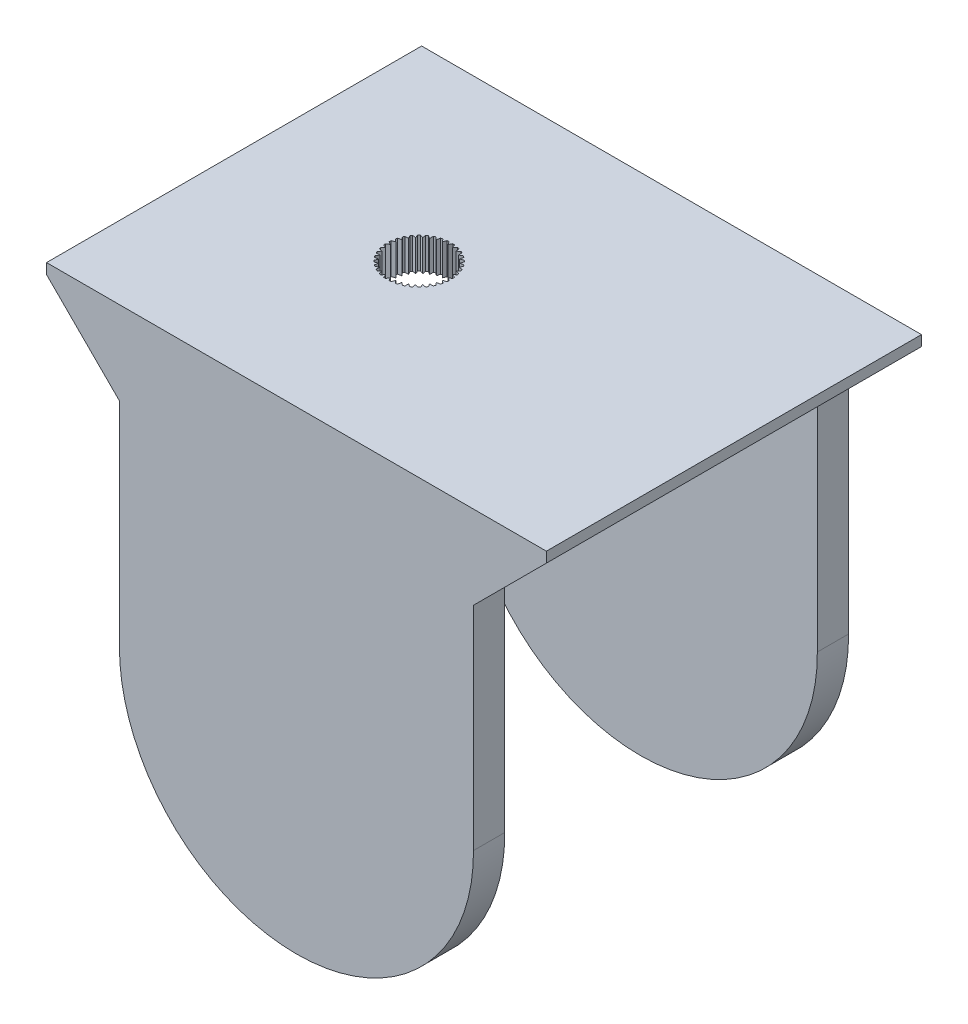
SolidWorks part; units mm, degrees
material "PLA"
ref_plane "Front Plane" through (0, 0, 0) normal (0, 0, 1) x (1, 0, 0)
ref_plane "Top Plane" through (0, 0, 0) normal (0, 1, 0) x (1, 0, 0)
ref_plane "Right Plane" through (0, 0, 0) normal (1, 0, 0) x (0, 0, -1)
sketch "Sketch1" plane through (0, 0, 0) normal (0, 1, 0) x (1, 0, 0)
  line L1 (-24, -18.01) -> (24, -18.01)
  line L2 (-24, -18.01) -> (-24, 18.01)
  line L3 (-24, 18.01) -> (24, 18.01)
  line L4 (24, -18.01) -> (24, 18.01)
  point P4 (0, 18.01)
  point P6 (-24, 0)
  dimension "D1" = 48
  dimension "D2" = 36.02
extrude "Boss-Extrude1" add sketch "Sketch1" along normal blind 3
sketch "Sketch2" plane through (0, 3, 0) normal (0, 1, 0) x (1, 0, 0)
  line L0 (2.3718, 1.5412) -> (2.4182, 1.6214) construction
  line L1 (2.3507, 1.7178) -> (2.2594, 1.7017) construction
  line L2 (2.4182, 1.6214) -> (2.4507, 1.6778) construction
  line L3 (2.4148, 1.7291) -> (2.3507, 1.7178) construction
  line L4 (2.2919, 1.4028) -> (2.3718, 1.5412) construction
  line L5 (2.2594, 1.7017) -> (2.1021, 1.6739) construction
  line L6 (2.0999, 2.0167) -> (2.1221, 2.0778) construction
  line L7 (2.0778, 2.1221) -> (2.0167, 2.0999) construction
  line L8 (2.0682, 1.9296) -> (2.0999, 2.0167) construction
  line L9 (2.0167, 2.0999) -> (1.9296, 2.0682) construction
  line L10 (2.0135, 1.7795) -> (2.0682, 1.9296) construction
  line L11 (1.9296, 2.0682) -> (1.7795, 2.0135) construction
  line L12 (1.6778, 2.4507) -> (1.6214, 2.4182) construction
  line L13 (1.7178, 2.3507) -> (1.7291, 2.4148) construction
  line L14 (1.6214, 2.4182) -> (1.5412, 2.3718) construction
  line L15 (1.7017, 2.2594) -> (1.7178, 2.3507) construction
  line L16 (1.5412, 2.3718) -> (1.4028, 2.2919) construction
  line L17 (1.6739, 2.1021) -> (1.7017, 2.2594) construction
  line L18 (2.5007, 0.9835) -> (2.6034, 1.1059) construction
  line L19 (2.5206, 1.2835) -> (2.3608, 1.2835) construction
  line L20 (2.663, 1.1768) -> (2.7048, 1.2267) construction
  line L21 (2.6783, 1.2835) -> (2.6132, 1.2835) construction
  line L22 (2.6034, 1.1059) -> (2.663, 1.1768) construction
  line L23 (2.6132, 1.2835) -> (2.5206, 1.2835) construction
  line L24 (2.8269, 0.6965) -> (2.8767, 0.7384) construction
  line L25 (2.8605, 0.7989) -> (2.7964, 0.8102) construction
  line L26 (2.7559, 0.637) -> (2.8269, 0.6965) construction
  line L27 (2.7964, 0.8102) -> (2.7052, 0.8263) construction
  line L28 (2.6335, 0.5343) -> (2.7559, 0.637) construction
  line L29 (2.7052, 0.8263) -> (2.5478, 0.854) construction
  line L30 (2.6863, 0.0689) -> (2.8247, 0.1488) construction
  line L31 (2.8076, 0.344) -> (2.6574, 0.3986) construction
  line L32 (2.8247, 0.1488) -> (2.9049, 0.1951) construction
  line L33 (2.8946, 0.3123) -> (2.8076, 0.344) construction
  line L34 (2.9049, 0.1951) -> (2.9613, 0.2276) construction
  line L35 (2.9558, 0.29) -> (2.8946, 0.3123) construction
  line L36 (2.9613, -0.2276) -> (2.9049, -0.1951) construction
  line L37 (2.8946, -0.3123) -> (2.9558, -0.29) construction
  line L38 (2.9049, -0.1951) -> (2.8247, -0.1488) construction
  line L39 (2.8076, -0.344) -> (2.8946, -0.3123) construction
  line L40 (2.8247, -0.1488) -> (2.6863, -0.0689) construction
  line L41 (2.6574, -0.3986) -> (2.8076, -0.344) construction
  line L42 (2.7964, -0.8102) -> (2.8605, -0.7989) construction
  line L43 (2.8767, -0.7384) -> (2.8269, -0.6965) construction
  line L44 (2.7052, -0.8263) -> (2.7964, -0.8102) construction
  line L45 (2.8269, -0.6965) -> (2.7559, -0.637) construction
  line L46 (2.5478, -0.854) -> (2.7052, -0.8263) construction
  line L47 (2.7559, -0.637) -> (2.6335, -0.5343) construction
  line L48 (2.5206, -1.2835) -> (2.6132, -1.2835) construction
  line L49 (2.663, -1.1768) -> (2.6034, -1.1059) construction
  line L50 (2.3608, -1.2835) -> (2.5206, -1.2835) construction
  line L51 (2.6034, -1.1059) -> (2.5007, -0.9835) construction
  line L52 (2.6863, -0.0689) -> (2.567, 0) construction
  line L53 (2.567, 0) -> (2.6863, 0.0689) construction
  line L54 (2.6574, 0.3986) -> (2.528, 0.4458) construction
  line L55 (2.528, 0.4458) -> (2.6335, 0.5343) construction
  line L56 (2.5478, 0.854) -> (2.4122, 0.878) construction
  line L57 (2.4122, 0.878) -> (2.5007, 0.9835) construction
  line L58 (2.3608, 1.2835) -> (2.2231, 1.2835) construction
  line L59 (2.2231, 1.2835) -> (2.2919, 1.4028) construction
  line L60 (2.1021, 1.6739) -> (1.9664, 1.65) construction
  line L61 (1.9664, 1.65) -> (2.0135, 1.7795) construction
  line L62 (1.7795, 2.0135) -> (1.65, 1.9664) construction
  line L63 (1.65, 1.9664) -> (1.6739, 2.1021) construction
  line L64 (1.4028, 2.2919) -> (1.2835, 2.2231) construction
  line L65 (1.2835, 2.2231) -> (1.2835, 2.3608) construction
  line L66 (0.9835, 2.5007) -> (0.878, 2.4122) construction
  line L67 (0.878, 2.4122) -> (0.854, 2.5478) construction
  line L68 (0.5343, 2.6335) -> (0.4458, 2.528) construction
  line L69 (0.4458, 2.528) -> (0.3986, 2.6574) construction
  line L70 (0.0689, 2.6863) -> (0, 2.567) construction
  line L71 (0, 2.567) -> (-0.0689, 2.6863) construction
  line L72 (-0.3986, 2.6574) -> (-0.4458, 2.528) construction
  line L73 (-0.4458, 2.528) -> (-0.5343, 2.6335) construction
  line L74 (-0.854, 2.5478) -> (-0.878, 2.4122) construction
  line L75 (-0.878, 2.4122) -> (-0.9835, 2.5007) construction
  line L76 (-1.2835, 2.3608) -> (-1.2835, 2.2231) construction
  line L77 (-1.2835, 2.2231) -> (-1.4028, 2.2919) construction
  line L78 (-1.6739, 2.1021) -> (-1.65, 1.9664) construction
  line L79 (-1.65, 1.9664) -> (-1.7795, 2.0135) construction
  line L80 (-2.0135, 1.7795) -> (-1.9664, 1.65) construction
  line L81 (-1.9664, 1.65) -> (-2.1021, 1.6739) construction
  line L82 (-2.2919, 1.4028) -> (-2.2231, 1.2835) construction
  line L83 (-2.2231, 1.2835) -> (-2.3608, 1.2835) construction
  line L84 (-2.5007, 0.9835) -> (-2.4122, 0.878) construction
  line L85 (-2.4122, 0.878) -> (-2.5478, 0.854) construction
  line L86 (-2.6335, 0.5343) -> (-2.528, 0.4458) construction
  line L87 (-2.528, 0.4458) -> (-2.6574, 0.3986) construction
  line L88 (-2.6863, 0.0689) -> (-2.567, 0) construction
  line L89 (-2.567, 0) -> (-2.6863, -0.0689) construction
  line L90 (-2.6574, -0.3986) -> (-2.528, -0.4458) construction
  line L91 (-2.528, -0.4458) -> (-2.6335, -0.5343) construction
  line L92 (-2.5478, -0.854) -> (-2.4122, -0.878) construction
  line L93 (-2.4122, -0.878) -> (-2.5007, -0.9835) construction
  line L94 (-2.3608, -1.2835) -> (-2.2231, -1.2835) construction
  line L95 (-2.2231, -1.2835) -> (-2.2919, -1.4028) construction
  line L96 (-2.1021, -1.6739) -> (-1.9664, -1.65) construction
  line L97 (-1.9664, -1.65) -> (-2.0135, -1.7795) construction
  line L98 (-1.7795, -2.0135) -> (-1.65, -1.9664) construction
  line L99 (-1.65, -1.9664) -> (-1.6739, -2.1021) construction
  line L100 (-1.4028, -2.2919) -> (-1.2835, -2.2231) construction
  line L101 (-1.2835, -2.2231) -> (-1.2835, -2.3608) construction
  line L102 (-0.9835, -2.5007) -> (-0.878, -2.4122) construction
  line L103 (-0.878, -2.4122) -> (-0.854, -2.5478) construction
  line L104 (-0.5343, -2.6335) -> (-0.4458, -2.528) construction
  line L105 (-0.4458, -2.528) -> (-0.3986, -2.6574) construction
  line L106 (-0.0689, -2.6863) -> (0, -2.567) construction
  line L107 (0, -2.567) -> (0.0689, -2.6863) construction
  line L108 (0.3986, -2.6574) -> (0.4458, -2.528) construction
  line L109 (0.4458, -2.528) -> (0.5343, -2.6335) construction
  line L110 (0.854, -2.5478) -> (0.878, -2.4122) construction
  line L111 (0.878, -2.4122) -> (0.9835, -2.5007) construction
  line L112 (1.2835, -2.3608) -> (1.2835, -2.2231) construction
  line L113 (1.2835, -2.2231) -> (1.4028, -2.2919) construction
  line L114 (1.6739, -2.1021) -> (1.65, -1.9664) construction
  line L115 (1.65, -1.9664) -> (1.7795, -2.0135) construction
  line L116 (2.0135, -1.7795) -> (1.9664, -1.65) construction
  line L117 (1.9664, -1.65) -> (2.1021, -1.6739) construction
  line L118 (2.2919, -1.4028) -> (2.2231, -1.2835) construction
  line L119 (2.2231, -1.2835) -> (2.3608, -1.2835) construction
  line L120 (2.5007, -0.9835) -> (2.4122, -0.878) construction
  line L121 (2.4122, -0.878) -> (2.5478, -0.854) construction
  line L122 (2.6335, -0.5343) -> (2.528, -0.4458) construction
  line L123 (2.528, -0.4458) -> (2.6574, -0.3986) construction
  line L124 (2.6132, -1.2835) -> (2.6783, -1.2835) construction
  line L125 (2.7048, -1.2267) -> (2.663, -1.1768) construction
  line L126 (2.4507, -1.6778) -> (2.4182, -1.6214) construction
  line L127 (2.3507, -1.7178) -> (2.4148, -1.7291) construction
  line L128 (2.4182, -1.6214) -> (2.3718, -1.5412) construction
  line L129 (2.2594, -1.7017) -> (2.3507, -1.7178) construction
  line L130 (1.7795, -2.0135) -> (1.9296, -2.0682) construction
  line L131 (2.0682, -1.9296) -> (2.0135, -1.7795) construction
  line L132 (1.9296, -2.0682) -> (2.0167, -2.0999) construction
  line L133 (2.0999, -2.0167) -> (2.0682, -1.9296) construction
  line L134 (2.0167, -2.0999) -> (2.0778, -2.1221) construction
  line L135 (2.1221, -2.0778) -> (2.0999, -2.0167) construction
  line L136 (2.3718, -1.5412) -> (2.2919, -1.4028) construction
  line L137 (2.1021, -1.6739) -> (2.2594, -1.7017) construction
  line L138 (1.7291, -2.4148) -> (1.7178, -2.3507) construction
  line L139 (1.6214, -2.4182) -> (1.6778, -2.4507) construction
  line L140 (1.7178, -2.3507) -> (1.7017, -2.2594) construction
  line L141 (1.5412, -2.3718) -> (1.6214, -2.4182) construction
  line L142 (1.7017, -2.2594) -> (1.6739, -2.1021) construction
  line L143 (1.4028, -2.2919) -> (1.5412, -2.3718) construction
  line L144 (-0.3123, -2.8946) -> (-0.29, -2.9558) construction
  line L145 (-0.2276, -2.9613) -> (-0.1951, -2.9049) construction
  line L146 (-0.344, -2.8076) -> (-0.3123, -2.8946) construction
  line L147 (-0.1951, -2.9049) -> (-0.1488, -2.8247) construction
  line L148 (0.344, -2.8076) -> (0.3986, -2.6574) construction
  line L149 (0.0689, -2.6863) -> (0.1488, -2.8247) construction
  line L150 (0.3123, -2.8946) -> (0.344, -2.8076) construction
  line L151 (0.1488, -2.8247) -> (0.1951, -2.9049) construction
  line L152 (0.29, -2.9558) -> (0.3123, -2.8946) construction
  line L153 (0.1951, -2.9049) -> (0.2276, -2.9613) construction
  line L154 (0.6965, -2.8269) -> (0.7384, -2.8767) construction
  line L155 (0.7989, -2.8605) -> (0.8102, -2.7964) construction
  line L156 (1.1768, -2.663) -> (1.2267, -2.7048) construction
  line L157 (1.2835, -2.6783) -> (1.2835, -2.6132) construction
  line L158 (1.1059, -2.6034) -> (1.1768, -2.663) construction
  line L159 (1.2835, -2.6132) -> (1.2835, -2.5206) construction
  line L160 (0.9835, -2.5007) -> (1.1059, -2.6034) construction
  line L161 (1.2835, -2.5206) -> (1.2835, -2.3608) construction
  line L162 (0.637, -2.7559) -> (0.6965, -2.8269) construction
  line L163 (0.8102, -2.7964) -> (0.8263, -2.7052) construction
  line L164 (0.5343, -2.6335) -> (0.637, -2.7559) construction
  line L165 (0.8263, -2.7052) -> (0.854, -2.5478) construction
  line L166 (-0.3986, -2.6574) -> (-0.344, -2.8076) construction
  line L167 (-0.1488, -2.8247) -> (-0.0689, -2.6863) construction
  line L168 (-0.8102, -2.7964) -> (-0.7989, -2.8605) construction
  line L169 (-0.7384, -2.8767) -> (-0.6965, -2.8269) construction
  line L170 (-0.8263, -2.7052) -> (-0.8102, -2.7964) construction
  line L171 (-0.6965, -2.8269) -> (-0.637, -2.7559) construction
  line L172 (-0.854, -2.5478) -> (-0.8263, -2.7052) construction
  line L173 (-0.637, -2.7559) -> (-0.5343, -2.6335) construction
  line L174 (-1.2835, -2.6132) -> (-1.2835, -2.6783) construction
  line L175 (-1.2267, -2.7048) -> (-1.1768, -2.663) construction
  line L176 (-1.2835, -2.5206) -> (-1.2835, -2.6132) construction
  line L177 (-1.1768, -2.663) -> (-1.1059, -2.6034) construction
  line L178 (-1.2835, -2.3608) -> (-1.2835, -2.5206) construction
  line L179 (-1.1059, -2.6034) -> (-0.9835, -2.5007) construction
  line L180 (-1.7178, -2.3507) -> (-1.7291, -2.4148) construction
  line L181 (-1.6778, -2.4507) -> (-1.6214, -2.4182) construction
  line L182 (-1.7017, -2.2594) -> (-1.7178, -2.3507) construction
  line L183 (-1.6214, -2.4182) -> (-1.5412, -2.3718) construction
  line L184 (-1.6739, -2.1021) -> (-1.7017, -2.2594) construction
  line L185 (-1.5412, -2.3718) -> (-1.4028, -2.2919) construction
  line L186 (-2.0999, -2.0167) -> (-2.1221, -2.0778) construction
  line L187 (-2.0778, -2.1221) -> (-2.0167, -2.0999) construction
  line L188 (-2.0682, -1.9296) -> (-2.0999, -2.0167) construction
  line L189 (-2.0167, -2.0999) -> (-1.9296, -2.0682) construction
  line L190 (-2.0135, -1.7795) -> (-2.0682, -1.9296) construction
  line L191 (-1.9296, -2.0682) -> (-1.7795, -2.0135) construction
  line L192 (-2.4148, -1.7291) -> (-2.3507, -1.7178) construction
  line L193 (-2.4182, -1.6214) -> (-2.4507, -1.6778) construction
  line L194 (-2.3507, -1.7178) -> (-2.2594, -1.7017) construction
  line L195 (-2.3718, -1.5412) -> (-2.4182, -1.6214) construction
  line L196 (-2.2594, -1.7017) -> (-2.1021, -1.6739) construction
  line L197 (-2.2919, -1.4028) -> (-2.3718, -1.5412) construction
  line L198 (-2.6783, -1.2835) -> (-2.6132, -1.2835) construction
  line L199 (-2.663, -1.1768) -> (-2.7048, -1.2267) construction
  line L200 (-2.6132, -1.2835) -> (-2.5206, -1.2835) construction
  line L201 (-2.6034, -1.1059) -> (-2.663, -1.1768) construction
  line L202 (-2.5206, -1.2835) -> (-2.3608, -1.2835) construction
  line L203 (-2.5007, -0.9835) -> (-2.6034, -1.1059) construction
  line L204 (-2.8605, -0.7989) -> (-2.7964, -0.8102) construction
  line L205 (-2.8269, -0.6965) -> (-2.8767, -0.7384) construction
  line L206 (-2.7964, -0.8102) -> (-2.7052, -0.8263) construction
  line L207 (-2.7559, -0.637) -> (-2.8269, -0.6965) construction
  line L208 (-2.7052, -0.8263) -> (-2.5478, -0.854) construction
  line L209 (-2.6335, -0.5343) -> (-2.7559, -0.637) construction
  line L210 (-2.9558, -0.29) -> (-2.8946, -0.3123) construction
  line L211 (-2.9049, -0.1951) -> (-2.9613, -0.2276) construction
  line L212 (-2.8076, -0.344) -> (-2.6574, -0.3986) construction
  line L213 (-2.6863, -0.0689) -> (-2.8247, -0.1488) construction
  line L214 (-2.8946, -0.3123) -> (-2.8076, -0.344) construction
  line L215 (-2.8247, -0.1488) -> (-2.9049, -0.1951) construction
  line L216 (-2.9613, 0.2276) -> (-2.9049, 0.1951) construction
  line L217 (-2.8946, 0.3123) -> (-2.9558, 0.29) construction
  line L218 (-2.9049, 0.1951) -> (-2.8247, 0.1488) construction
  line L219 (-2.8076, 0.344) -> (-2.8946, 0.3123) construction
  line L220 (-2.8247, 0.1488) -> (-2.6863, 0.0689) construction
  line L221 (-2.6574, 0.3986) -> (-2.8076, 0.344) construction
  line L222 (-2.8269, 0.6965) -> (-2.7559, 0.637) construction
  line L223 (-2.7052, 0.8263) -> (-2.7964, 0.8102) construction
  line L224 (-2.8767, 0.7384) -> (-2.8269, 0.6965) construction
  line L225 (-2.7964, 0.8102) -> (-2.8605, 0.7989) construction
  line L226 (-2.7559, 0.637) -> (-2.6335, 0.5343) construction
  line L227 (-2.5478, 0.854) -> (-2.7052, 0.8263) construction
  line L228 (-2.663, 1.1768) -> (-2.6034, 1.1059) construction
  line L229 (-2.5206, 1.2835) -> (-2.6132, 1.2835) construction
  line L230 (-2.7048, 1.2267) -> (-2.663, 1.1768) construction
  line L231 (-2.6132, 1.2835) -> (-2.6783, 1.2835) construction
  line L232 (-2.6034, 1.1059) -> (-2.5007, 0.9835) construction
  line L233 (-2.3608, 1.2835) -> (-2.5206, 1.2835) construction
  line L234 (-2.4507, 1.6778) -> (-2.4182, 1.6214) construction
  line L235 (-2.3507, 1.7178) -> (-2.4148, 1.7291) construction
  line L236 (-2.4182, 1.6214) -> (-2.3718, 1.5412) construction
  line L237 (-2.2594, 1.7017) -> (-2.3507, 1.7178) construction
  line L238 (-2.3718, 1.5412) -> (-2.2919, 1.4028) construction
  line L239 (-2.1021, 1.6739) -> (-2.2594, 1.7017) construction
  line L240 (-2.0167, 2.0999) -> (-2.0778, 2.1221) construction
  line L241 (-2.1221, 2.0778) -> (-2.0999, 2.0167) construction
  line L242 (-1.9296, 2.0682) -> (-2.0167, 2.0999) construction
  line L243 (-2.0999, 2.0167) -> (-2.0682, 1.9296) construction
  line L244 (-1.7795, 2.0135) -> (-1.9296, 2.0682) construction
  line L245 (-2.0682, 1.9296) -> (-2.0135, 1.7795) construction
  line L246 (-1.7291, 2.4148) -> (-1.7178, 2.3507) construction
  line L247 (-1.6214, 2.4182) -> (-1.6778, 2.4507) construction
  line L248 (-1.7178, 2.3507) -> (-1.7017, 2.2594) construction
  line L249 (-1.5412, 2.3718) -> (-1.6214, 2.4182) construction
  line L250 (-1.7017, 2.2594) -> (-1.6739, 2.1021) construction
  line L251 (-1.4028, 2.2919) -> (-1.5412, 2.3718) construction
  line L252 (-1.2835, 2.6783) -> (-1.2835, 2.6132) construction
  line L253 (-1.1768, 2.663) -> (-1.2267, 2.7048) construction
  line L254 (-1.2835, 2.6132) -> (-1.2835, 2.5206) construction
  line L255 (-1.1059, 2.6034) -> (-1.1768, 2.663) construction
  line L256 (-1.2835, 2.5206) -> (-1.2835, 2.3608) construction
  line L257 (-0.9835, 2.5007) -> (-1.1059, 2.6034) construction
  line L258 (-0.7989, 2.8605) -> (-0.8102, 2.7964) construction
  line L259 (-0.6965, 2.8269) -> (-0.7384, 2.8767) construction
  line L260 (-0.8102, 2.7964) -> (-0.8263, 2.7052) construction
  line L261 (-0.637, 2.7559) -> (-0.6965, 2.8269) construction
  line L262 (-0.8263, 2.7052) -> (-0.854, 2.5478) construction
  line L263 (-0.5343, 2.6335) -> (-0.637, 2.7559) construction
  line L264 (1.1768, 2.663) -> (1.1059, 2.6034) construction
  line L265 (1.2835, 2.5206) -> (1.2835, 2.6132) construction
  line L266 (1.2267, 2.7048) -> (1.1768, 2.663) construction
  line L267 (1.2835, 2.6132) -> (1.2835, 2.6783) construction
  line L268 (1.1059, 2.6034) -> (0.9835, 2.5007) construction
  line L269 (1.2835, 2.3608) -> (1.2835, 2.5206) construction
  line L270 (0.8102, 2.7964) -> (0.7989, 2.8605) construction
  line L271 (0.7384, 2.8767) -> (0.6965, 2.8269) construction
  line L272 (0.8263, 2.7052) -> (0.8102, 2.7964) construction
  line L273 (0.6965, 2.8269) -> (0.637, 2.7559) construction
  line L274 (0.854, 2.5478) -> (0.8263, 2.7052) construction
  line L275 (0.637, 2.7559) -> (0.5343, 2.6335) construction
  line L276 (0.3123, 2.8946) -> (0.29, 2.9558) construction
  line L277 (0.2276, 2.9613) -> (0.1951, 2.9049) construction
  line L278 (0.344, 2.8076) -> (0.3123, 2.8946) construction
  line L279 (0.1951, 2.9049) -> (0.1488, 2.8247) construction
  line L280 (0.3986, 2.6574) -> (0.344, 2.8076) construction
  line L281 (0.1488, 2.8247) -> (0.0689, 2.6863) construction
  line L282 (-0.29, 2.9558) -> (-0.3123, 2.8946) construction
  line L283 (-0.1951, 2.9049) -> (-0.2276, 2.9613) construction
  line L284 (-0.3123, 2.8946) -> (-0.344, 2.8076) construction
  line L285 (-0.1488, 2.8247) -> (-0.1951, 2.9049) construction
  line L286 (-0.344, 2.8076) -> (-0.3986, 2.6574) construction
  line L287 (-0.0689, 2.6863) -> (-0.1488, 2.8247) construction
  line L288 (2.4584, 1.4912) -> (2.5048, 1.5714)
  line L289 (2.5048, 1.5714) -> (2.5684, 1.6817)
  line L290 (2.4587, 1.8384) -> (2.3333, 1.8163)
  line L291 (2.3333, 1.8163) -> (2.2421, 1.8002)
  line L292 (2.2421, 1.8002) -> (2.1196, 1.7786)
  line L293 (2.1196, 1.7786) -> (2.1196, 1.7786)
  line L294 (2.1196, 1.7786) -> (2.1196, 1.7786)
  line L295 (2.1196, 1.7786) -> (2.1622, 1.8954)
  line L296 (2.1622, 1.8954) -> (2.1938, 1.9825)
  line L297 (2.1938, 1.9825) -> (2.2374, 2.1021)
  line L298 (2.1021, 2.2374) -> (1.9825, 2.1938)
  line L299 (1.9825, 2.1938) -> (1.8954, 2.1622)
  line L300 (1.8954, 2.1622) -> (1.7786, 2.1196)
  line L301 (1.7786, 2.1196) -> (1.7786, 2.1196)
  line L302 (1.7786, 2.1196) -> (1.7786, 2.1196)
  line L303 (1.7786, 2.1196) -> (1.8002, 2.2421)
  line L304 (1.8002, 2.2421) -> (1.8163, 2.3333)
  line L305 (1.8163, 2.3333) -> (1.8384, 2.4587)
  line L306 (1.6817, 2.5684) -> (1.5714, 2.5048)
  line L307 (1.5714, 2.5048) -> (1.4912, 2.4584)
  line L308 (1.4912, 2.4584) -> (1.3835, 2.3963)
  line L309 (1.3835, 2.3963) -> (1.3835, 2.3963)
  line L310 (1.3835, 2.3963) -> (1.3835, 2.3963)
  line L311 (1.3835, 2.3963) -> (1.3835, 2.5206)
  line L312 (1.3835, 2.5206) -> (1.3835, 2.6132)
  line L313 (1.3835, 2.6132) -> (1.3835, 2.7406)
  line L314 (1.2101, 2.8214) -> (1.1126, 2.7396)
  line L315 (1.1126, 2.7396) -> (1.0416, 2.68)
  line L316 (1.0416, 2.68) -> (0.9464, 2.6001)
  line L317 (0.9464, 2.6001) -> (0.9464, 2.6001)
  line L318 (0.9464, 2.6001) -> (0.9464, 2.6001)
  line L319 (0.9464, 2.6001) -> (0.9248, 2.7226)
  line L320 (0.9248, 2.7226) -> (0.9087, 2.8138)
  line L321 (0.9087, 2.8138) -> (0.8866, 2.9392)
  line L322 (0.7018, 2.9887) -> (0.6199, 2.8911)
  line L323 (0.6199, 2.8911) -> (0.5604, 2.8202)
  line L324 (0.5604, 2.8202) -> (0.4805, 2.725)
  line L325 (0.4805, 2.725) -> (0.4805, 2.725)
  line L326 (0.4805, 2.725) -> (0.4805, 2.725)
  line L327 (0.4805, 2.725) -> (0.438, 2.8418)
  line L328 (0.438, 2.8418) -> (0.4063, 2.9288)
  line L329 (0.4063, 2.9288) -> (0.3627, 3.0485)
  line L330 (0.1722, 3.0652) -> (0.1085, 2.9549)
  line L331 (0.1085, 2.9549) -> (0.0622, 2.8747)
  line L332 (0.0622, 2.8747) -> (0, 2.767)
  line L333 (0, 2.767) -> (0, 2.767)
  line L334 (0, 2.767) -> (0, 2.767)
  line L335 (0, 2.767) -> (-0.0622, 2.8747)
  line L336 (-0.0622, 2.8747) -> (-0.1085, 2.9549)
  line L337 (-0.1085, 2.9549) -> (-0.1722, 3.0652)
  line L338 (-0.3627, 3.0485) -> (-0.4063, 2.9288)
  line L339 (-0.4063, 2.9288) -> (-0.438, 2.8418)
  line L340 (-0.438, 2.8418) -> (-0.4805, 2.725)
  line L341 (-0.4805, 2.725) -> (-0.4805, 2.725)
  line L342 (-0.4805, 2.725) -> (-0.4805, 2.725)
  line L343 (-0.4805, 2.725) -> (-0.5604, 2.8202)
  line L344 (-0.5604, 2.8202) -> (-0.6199, 2.8911)
  line L345 (-0.6199, 2.8911) -> (-0.7018, 2.9887)
  line L346 (-0.8866, 2.9392) -> (-0.9087, 2.8138)
  line L347 (-0.9087, 2.8138) -> (-0.9248, 2.7226)
  line L348 (-0.9248, 2.7226) -> (-0.9464, 2.6001)
  line L349 (-0.9464, 2.6001) -> (-0.9464, 2.6001)
  line L350 (-0.9464, 2.6001) -> (-0.9464, 2.6001)
  line L351 (-0.9464, 2.6001) -> (-1.0416, 2.68)
  line L352 (-1.0416, 2.68) -> (-1.1126, 2.7396)
  line L353 (-1.1126, 2.7396) -> (-1.2101, 2.8214)
  line L354 (-1.3835, 2.7406) -> (-1.3835, 2.6132)
  line L355 (-1.3835, 2.6132) -> (-1.3835, 2.5206)
  line L356 (-1.3835, 2.5206) -> (-1.3835, 2.3963)
  line L357 (-1.3835, 2.3963) -> (-1.3835, 2.3963)
  line L358 (-1.3835, 2.3963) -> (-1.3835, 2.3963)
  line L359 (-1.3835, 2.3963) -> (-1.4912, 2.4584)
  line L360 (-1.4912, 2.4584) -> (-1.5714, 2.5048)
  line L361 (-1.5714, 2.5048) -> (-1.6817, 2.5684)
  line L362 (-1.8384, 2.4587) -> (-1.8163, 2.3333)
  line L363 (-1.8163, 2.3333) -> (-1.8002, 2.2421)
  line L364 (-1.8002, 2.2421) -> (-1.7786, 2.1196)
  line L365 (-1.7786, 2.1196) -> (-1.7786, 2.1196)
  line L366 (-1.7786, 2.1196) -> (-1.7786, 2.1196)
  line L367 (-1.7786, 2.1196) -> (-1.8954, 2.1622)
  line L368 (-1.8954, 2.1622) -> (-1.9825, 2.1938)
  line L369 (-1.9825, 2.1938) -> (-2.1021, 2.2374)
  line L370 (-2.2374, 2.1021) -> (-2.1938, 1.9825)
  line L371 (-2.1938, 1.9825) -> (-2.1622, 1.8954)
  line L372 (-2.1622, 1.8954) -> (-2.1196, 1.7786)
  line L373 (-2.1196, 1.7786) -> (-2.1196, 1.7786)
  line L374 (-2.1196, 1.7786) -> (-2.1196, 1.7786)
  line L375 (-2.1196, 1.7786) -> (-2.2421, 1.8002)
  line L376 (-2.2421, 1.8002) -> (-2.3333, 1.8163)
  line L377 (-2.3333, 1.8163) -> (-2.4587, 1.8384)
  line L378 (-2.5684, 1.6817) -> (-2.5048, 1.5714)
  line L379 (-2.5048, 1.5714) -> (-2.4584, 1.4912)
  line L380 (-2.4584, 1.4912) -> (-2.3963, 1.3835)
  line L381 (-2.3963, 1.3835) -> (-2.3963, 1.3835)
  line L382 (-2.3963, 1.3835) -> (-2.3963, 1.3835)
  line L383 (-2.3963, 1.3835) -> (-2.5206, 1.3835)
  line L384 (-2.5206, 1.3835) -> (-2.6132, 1.3835)
  line L385 (-2.6132, 1.3835) -> (-2.7406, 1.3835)
  line L386 (-2.8214, 1.2101) -> (-2.7396, 1.1126)
  line L387 (-2.7396, 1.1126) -> (-2.68, 1.0416)
  line L388 (-2.68, 1.0416) -> (-2.6001, 0.9464)
  line L389 (-2.6001, 0.9464) -> (-2.6001, 0.9464)
  line L390 (-2.6001, 0.9464) -> (-2.6001, 0.9464)
  line L391 (-2.6001, 0.9464) -> (-2.7226, 0.9248)
  line L392 (-2.7226, 0.9248) -> (-2.8138, 0.9087)
  line L393 (-2.8138, 0.9087) -> (-2.9392, 0.8866)
  line L394 (-2.9887, 0.7018) -> (-2.8911, 0.6199)
  line L395 (-2.8911, 0.6199) -> (-2.8202, 0.5604)
  line L396 (-2.8202, 0.5604) -> (-2.725, 0.4805)
  line L397 (-2.725, 0.4805) -> (-2.725, 0.4805)
  line L398 (-2.725, 0.4805) -> (-2.725, 0.4805)
  line L399 (-2.725, 0.4805) -> (-2.8418, 0.438)
  line L400 (-2.8418, 0.438) -> (-2.9288, 0.4063)
  line L401 (-2.9288, 0.4063) -> (-3.0485, 0.3627)
  line L402 (-3.0652, 0.1722) -> (-2.9549, 0.1085)
  line L403 (-2.9549, 0.1085) -> (-2.8747, 0.0622)
  line L404 (-2.8747, 0.0622) -> (-2.767, 0)
  line L405 (-2.767, 0) -> (-2.767, 0)
  line L406 (-2.767, 0) -> (-2.767, 0)
  line L407 (-2.767, 0) -> (-2.8747, -0.0622)
  line L408 (-2.8747, -0.0622) -> (-2.9549, -0.1085)
  line L409 (-2.9549, -0.1085) -> (-3.0652, -0.1722)
  line L410 (-3.0485, -0.3627) -> (-2.9288, -0.4063)
  line L411 (-2.9288, -0.4063) -> (-2.8418, -0.438)
  line L412 (-2.8418, -0.438) -> (-2.725, -0.4805)
  line L413 (-2.725, -0.4805) -> (-2.725, -0.4805)
  line L414 (-2.725, -0.4805) -> (-2.725, -0.4805)
  line L415 (-2.725, -0.4805) -> (-2.8202, -0.5604)
  line L416 (-2.8202, -0.5604) -> (-2.8911, -0.6199)
  line L417 (-2.8911, -0.6199) -> (-2.9887, -0.7018)
  line L418 (-2.9392, -0.8866) -> (-2.8138, -0.9087)
  line L419 (-2.8138, -0.9087) -> (-2.7226, -0.9248)
  line L420 (-2.7226, -0.9248) -> (-2.6001, -0.9464)
  line L421 (-2.6001, -0.9464) -> (-2.6001, -0.9464)
  line L422 (-2.6001, -0.9464) -> (-2.6001, -0.9464)
  line L423 (-2.6001, -0.9464) -> (-2.68, -1.0416)
  line L424 (-2.68, -1.0416) -> (-2.7396, -1.1126)
  line L425 (-2.7396, -1.1126) -> (-2.8214, -1.2101)
  line L426 (-2.7406, -1.3835) -> (-2.6132, -1.3835)
  line L427 (-2.6132, -1.3835) -> (-2.5206, -1.3835)
  line L428 (-2.5206, -1.3835) -> (-2.3963, -1.3835)
  line L429 (-2.3963, -1.3835) -> (-2.3963, -1.3835)
  line L430 (-2.3963, -1.3835) -> (-2.3963, -1.3835)
  line L431 (-2.3963, -1.3835) -> (-2.4584, -1.4912)
  line L432 (-2.4584, -1.4912) -> (-2.5048, -1.5714)
  line L433 (-2.5048, -1.5714) -> (-2.5684, -1.6817)
  line L434 (-2.4587, -1.8384) -> (-2.3333, -1.8163)
  line L435 (-2.3333, -1.8163) -> (-2.2421, -1.8002)
  line L436 (-2.2421, -1.8002) -> (-2.1196, -1.7786)
  line L437 (-2.1196, -1.7786) -> (-2.1196, -1.7786)
  line L438 (-2.1196, -1.7786) -> (-2.1196, -1.7786)
  line L439 (-2.1196, -1.7786) -> (-2.1622, -1.8954)
  line L440 (-2.1622, -1.8954) -> (-2.1938, -1.9825)
  line L441 (-2.1938, -1.9825) -> (-2.2374, -2.1021)
  line L442 (-2.1021, -2.2374) -> (-1.9825, -2.1938)
  line L443 (-1.9825, -2.1938) -> (-1.8954, -2.1622)
  line L444 (-1.8954, -2.1622) -> (-1.7786, -2.1196)
  line L445 (-1.7786, -2.1196) -> (-1.7786, -2.1196)
  line L446 (-1.7786, -2.1196) -> (-1.7786, -2.1196)
  line L447 (-1.7786, -2.1196) -> (-1.8002, -2.2421)
  line L448 (-1.8002, -2.2421) -> (-1.8163, -2.3333)
  line L449 (-1.8163, -2.3333) -> (-1.8384, -2.4587)
  line L450 (-1.6817, -2.5684) -> (-1.5714, -2.5048)
  line L451 (-1.5714, -2.5048) -> (-1.4912, -2.4584)
  line L452 (-1.4912, -2.4584) -> (-1.3835, -2.3963)
  line L453 (-1.3835, -2.3963) -> (-1.3835, -2.3963)
  line L454 (-1.3835, -2.3963) -> (-1.3835, -2.3963)
  line L455 (-1.3835, -2.3963) -> (-1.3835, -2.5206)
  line L456 (-1.3835, -2.5206) -> (-1.3835, -2.6132)
  line L457 (-1.3835, -2.6132) -> (-1.3835, -2.7406)
  line L458 (-1.2101, -2.8214) -> (-1.1126, -2.7396)
  line L459 (-1.1126, -2.7396) -> (-1.0416, -2.68)
  line L460 (-1.0416, -2.68) -> (-0.9464, -2.6001)
  line L461 (-0.9464, -2.6001) -> (-0.9464, -2.6001)
  line L462 (-0.9464, -2.6001) -> (-0.9464, -2.6001)
  line L463 (-0.9464, -2.6001) -> (-0.9248, -2.7226)
  line L464 (-0.9248, -2.7226) -> (-0.9087, -2.8138)
  line L465 (-0.9087, -2.8138) -> (-0.8866, -2.9392)
  line L466 (-0.7018, -2.9887) -> (-0.6199, -2.8911)
  line L467 (-0.6199, -2.8911) -> (-0.5604, -2.8202)
  line L468 (-0.5604, -2.8202) -> (-0.4805, -2.725)
  line L469 (-0.4805, -2.725) -> (-0.4805, -2.725)
  line L470 (-0.4805, -2.725) -> (-0.4805, -2.725)
  line L471 (-0.4805, -2.725) -> (-0.438, -2.8418)
  line L472 (-0.438, -2.8418) -> (-0.4063, -2.9288)
  line L473 (-0.4063, -2.9288) -> (-0.3627, -3.0485)
  line L474 (-0.1722, -3.0652) -> (-0.1085, -2.9549)
  line L475 (-0.1085, -2.9549) -> (-0.0622, -2.8747)
  line L476 (-0.0622, -2.8747) -> (0, -2.767)
  line L477 (0, -2.767) -> (0, -2.767)
  line L478 (0, -2.767) -> (0, -2.767)
  line L479 (0, -2.767) -> (0.0622, -2.8747)
  line L480 (0.0622, -2.8747) -> (0.1085, -2.9549)
  line L481 (0.1085, -2.9549) -> (0.1722, -3.0652)
  line L482 (0.3627, -3.0485) -> (0.4063, -2.9288)
  line L483 (0.4063, -2.9288) -> (0.438, -2.8418)
  line L484 (0.438, -2.8418) -> (0.4805, -2.725)
  line L485 (0.4805, -2.725) -> (0.4805, -2.725)
  line L486 (0.4805, -2.725) -> (0.4805, -2.725)
  line L487 (0.4805, -2.725) -> (0.5604, -2.8202)
  line L488 (0.5604, -2.8202) -> (0.6199, -2.8911)
  line L489 (0.6199, -2.8911) -> (0.7018, -2.9887)
  line L490 (0.8866, -2.9392) -> (0.9087, -2.8138)
  line L491 (0.9087, -2.8138) -> (0.9248, -2.7226)
  line L492 (0.9248, -2.7226) -> (0.9464, -2.6001)
  line L493 (0.9464, -2.6001) -> (0.9464, -2.6001)
  line L494 (0.9464, -2.6001) -> (0.9464, -2.6001)
  line L495 (0.9464, -2.6001) -> (1.0416, -2.68)
  line L496 (1.0416, -2.68) -> (1.1126, -2.7396)
  line L497 (1.1126, -2.7396) -> (1.2101, -2.8214)
  line L498 (1.3835, -2.7406) -> (1.3835, -2.6132)
  line L499 (1.3835, -2.6132) -> (1.3835, -2.5206)
  line L500 (1.3835, -2.5206) -> (1.3835, -2.3963)
  line L501 (1.3835, -2.3963) -> (1.3835, -2.3963)
  line L502 (1.3835, -2.3963) -> (1.3835, -2.3963)
  line L503 (1.3835, -2.3963) -> (1.4912, -2.4584)
  line L504 (1.4912, -2.4584) -> (1.5714, -2.5048)
  line L505 (1.5714, -2.5048) -> (1.6817, -2.5684)
  line L506 (1.8384, -2.4587) -> (1.8163, -2.3333)
  line L507 (1.8163, -2.3333) -> (1.8002, -2.2421)
  line L508 (1.8002, -2.2421) -> (1.7786, -2.1196)
  line L509 (1.7786, -2.1196) -> (1.7786, -2.1196)
  line L510 (1.7786, -2.1196) -> (1.7786, -2.1196)
  line L511 (1.7786, -2.1196) -> (1.8954, -2.1622)
  line L512 (1.8954, -2.1622) -> (1.9825, -2.1938)
  line L513 (1.9825, -2.1938) -> (2.1021, -2.2374)
  line L514 (2.2374, -2.1021) -> (2.1938, -1.9825)
  line L515 (2.1938, -1.9825) -> (2.1622, -1.8954)
  line L516 (2.1622, -1.8954) -> (2.1196, -1.7786)
  line L517 (2.1196, -1.7786) -> (2.1196, -1.7786)
  line L518 (2.1196, -1.7786) -> (2.1196, -1.7786)
  line L519 (2.1196, -1.7786) -> (2.2421, -1.8002)
  line L520 (2.2421, -1.8002) -> (2.3333, -1.8163)
  line L521 (2.3333, -1.8163) -> (2.4587, -1.8384)
  line L522 (2.5684, -1.6817) -> (2.5048, -1.5714)
  line L523 (2.5048, -1.5714) -> (2.4584, -1.4912)
  line L524 (2.4584, -1.4912) -> (2.3963, -1.3835)
  line L525 (2.3963, -1.3835) -> (2.3963, -1.3835)
  line L526 (2.3963, -1.3835) -> (2.3963, -1.3835)
  line L527 (2.3963, -1.3835) -> (2.5206, -1.3835)
  line L528 (2.5206, -1.3835) -> (2.6132, -1.3835)
  line L529 (2.6132, -1.3835) -> (2.7406, -1.3835)
  line L530 (2.8214, -1.2101) -> (2.7396, -1.1126)
  line L531 (2.7396, -1.1126) -> (2.68, -1.0416)
  line L532 (2.68, -1.0416) -> (2.6001, -0.9464)
  line L533 (2.6001, -0.9464) -> (2.6001, -0.9464)
  line L534 (2.6001, -0.9464) -> (2.6001, -0.9464)
  line L535 (2.6001, -0.9464) -> (2.7226, -0.9248)
  line L536 (2.7226, -0.9248) -> (2.8138, -0.9087)
  line L537 (2.8138, -0.9087) -> (2.9392, -0.8866)
  line L538 (2.9887, -0.7018) -> (2.8911, -0.6199)
  line L539 (2.8911, -0.6199) -> (2.8202, -0.5604)
  line L540 (2.8202, -0.5604) -> (2.725, -0.4805)
  line L541 (2.725, -0.4805) -> (2.725, -0.4805)
  line L542 (2.725, -0.4805) -> (2.725, -0.4805)
  line L543 (2.725, -0.4805) -> (2.8418, -0.438)
  line L544 (2.8418, -0.438) -> (2.9288, -0.4063)
  line L545 (2.9288, -0.4063) -> (3.0485, -0.3627)
  line L546 (3.0652, -0.1722) -> (2.9549, -0.1085)
  line L547 (2.9549, -0.1085) -> (2.8747, -0.0622)
  line L548 (2.8747, -0.0622) -> (2.767, 0)
  line L549 (2.767, 0) -> (2.767, 0)
  line L550 (2.767, 0) -> (2.767, 0)
  line L551 (2.767, 0) -> (2.8747, 0.0622)
  line L552 (2.8747, 0.0622) -> (2.9549, 0.1085)
  line L553 (2.9549, 0.1085) -> (3.0652, 0.1722)
  line L554 (3.0485, 0.3627) -> (2.9288, 0.4063)
  line L555 (2.9288, 0.4063) -> (2.8418, 0.438)
  line L556 (2.8418, 0.438) -> (2.725, 0.4805)
  line L557 (2.725, 0.4805) -> (2.725, 0.4805)
  line L558 (2.725, 0.4805) -> (2.725, 0.4805)
  line L559 (2.725, 0.4805) -> (2.8202, 0.5604)
  line L560 (2.8202, 0.5604) -> (2.8911, 0.6199)
  line L561 (2.8911, 0.6199) -> (2.9887, 0.7018)
  line L562 (2.9392, 0.8866) -> (2.8138, 0.9087)
  line L563 (2.8138, 0.9087) -> (2.7226, 0.9248)
  line L564 (2.7226, 0.9248) -> (2.6001, 0.9464)
  line L565 (2.6001, 0.9464) -> (2.6001, 0.9464)
  line L566 (2.6001, 0.9464) -> (2.6001, 0.9464)
  line L567 (2.6001, 0.9464) -> (2.68, 1.0416)
  line L568 (2.68, 1.0416) -> (2.7396, 1.1126)
  line L569 (2.7396, 1.1126) -> (2.8214, 1.2101)
  line L570 (2.7406, 1.3835) -> (2.6132, 1.3835)
  line L571 (2.6132, 1.3835) -> (2.5206, 1.3835)
  line L572 (2.5206, 1.3835) -> (2.3963, 1.3835)
  line L573 (2.3963, 1.3835) -> (2.3963, 1.3835)
  line L574 (2.3963, 1.3835) -> (2.3963, 1.3835)
  line L575 (2.3963, 1.3835) -> (2.4584, 1.4912)
  arc A0 (2.4507, 1.6778) -> (2.4148, 1.7291) centre (0, 0) ccw construction
  arc A1 (2.1221, 2.0778) -> (2.0778, 2.1221) centre (0, 0) ccw construction
  arc A2 (1.7291, 2.4148) -> (1.6778, 2.4507) centre (0, 0) ccw construction
  arc A3 (2.7048, 1.2267) -> (2.6783, 1.2835) centre (0, 0) ccw construction
  arc A4 (2.8767, 0.7384) -> (2.8605, 0.7989) centre (0, 0) ccw construction
  arc A5 (2.9613, 0.2276) -> (2.9558, 0.29) centre (0, 0) ccw construction
  arc A6 (2.9558, -0.29) -> (2.9613, -0.2276) centre (0, 0) ccw construction
  arc A7 (2.8605, -0.7989) -> (2.8767, -0.7384) centre (0, 0) ccw construction
  arc A8 (2.6783, -1.2835) -> (2.7048, -1.2267) centre (0, 0) ccw construction
  arc A9 (2.4148, -1.7291) -> (2.4507, -1.6778) centre (0, 0) ccw construction
  arc A10 (2.0778, -2.1221) -> (2.1221, -2.0778) centre (0, 0) ccw construction
  arc A11 (1.6778, -2.4507) -> (1.7291, -2.4148) centre (0, 0) ccw construction
  arc A12 (-0.29, -2.9558) -> (-0.2276, -2.9613) centre (0, 0) ccw construction
  arc A13 (0.2276, -2.9613) -> (0.29, -2.9558) centre (0, 0) ccw construction
  arc A14 (0.7384, -2.8767) -> (0.7989, -2.8605) centre (0, 0) ccw construction
  arc A15 (1.2267, -2.7048) -> (1.2835, -2.6783) centre (0, 0) ccw construction
  arc A16 (-0.7989, -2.8605) -> (-0.7384, -2.8767) centre (0, 0) ccw construction
  arc A17 (-1.2835, -2.6783) -> (-1.2267, -2.7048) centre (0, 0) ccw construction
  arc A18 (-1.7291, -2.4148) -> (-1.6778, -2.4507) centre (0, 0) ccw construction
  arc A19 (-2.1221, -2.0778) -> (-2.0778, -2.1221) centre (0, 0) ccw construction
  arc A20 (-2.4507, -1.6778) -> (-2.4148, -1.7291) centre (0, 0) ccw construction
  arc A21 (-2.7048, -1.2267) -> (-2.6783, -1.2835) centre (0, 0) ccw construction
  arc A22 (-2.8767, -0.7384) -> (-2.8605, -0.7989) centre (0, 0) ccw construction
  arc A23 (-2.9613, -0.2276) -> (-2.9558, -0.29) centre (0, 0) ccw construction
  arc A24 (-2.9558, 0.29) -> (-2.9613, 0.2276) centre (0, 0) ccw construction
  arc A25 (-2.8605, 0.7989) -> (-2.8767, 0.7384) centre (0, 0) ccw construction
  arc A26 (-2.6783, 1.2835) -> (-2.7048, 1.2267) centre (0, 0) ccw construction
  arc A27 (-2.4148, 1.7291) -> (-2.4507, 1.6778) centre (0, 0) ccw construction
  arc A28 (-2.0778, 2.1221) -> (-2.1221, 2.0778) centre (0, 0) ccw construction
  arc A29 (-1.6778, 2.4507) -> (-1.7291, 2.4148) centre (0, 0) ccw construction
  arc A30 (-1.2267, 2.7048) -> (-1.2835, 2.6783) centre (0, 0) ccw construction
  arc A31 (-0.7384, 2.8767) -> (-0.7989, 2.8605) centre (0, 0) ccw construction
  arc A32 (1.2835, 2.6783) -> (1.2267, 2.7048) centre (0, 0) ccw construction
  arc A33 (0.7989, 2.8605) -> (0.7384, 2.8767) centre (0, 0) ccw construction
  arc A34 (0.29, 2.9558) -> (0.2276, 2.9613) centre (0, 0) ccw construction
  arc A35 (-0.2276, 2.9613) -> (-0.29, 2.9558) centre (0, 0) ccw construction
  arc A36 (2.5684, 1.6817) -> (2.4587, 1.8384) centre (0, 0) ccw
  arc A37 (2.2374, 2.1021) -> (2.1021, 2.2374) centre (0, 0) ccw
  arc A38 (1.8384, 2.4587) -> (1.6817, 2.5684) centre (0, 0) ccw
  arc A39 (1.3835, 2.7406) -> (1.2101, 2.8214) centre (0, 0) ccw
  arc A40 (0.8866, 2.9392) -> (0.7018, 2.9887) centre (0, 0) ccw
  arc A41 (0.3627, 3.0485) -> (0.1722, 3.0652) centre (0, 0) ccw
  arc A42 (-0.1722, 3.0652) -> (-0.3627, 3.0485) centre (0, 0) ccw
  arc A43 (-0.7018, 2.9887) -> (-0.8866, 2.9392) centre (0, 0) ccw
  arc A44 (-1.2101, 2.8214) -> (-1.3835, 2.7406) centre (0, 0) ccw
  arc A45 (-1.6817, 2.5684) -> (-1.8384, 2.4587) centre (0, 0) ccw
  arc A46 (-2.1021, 2.2374) -> (-2.2374, 2.1021) centre (0, 0) ccw
  arc A47 (-2.4587, 1.8384) -> (-2.5684, 1.6817) centre (0, 0) ccw
  arc A48 (-2.7406, 1.3835) -> (-2.8214, 1.2101) centre (0, 0) ccw
  arc A49 (-2.9392, 0.8866) -> (-2.9887, 0.7018) centre (0, 0) ccw
  arc A50 (-3.0485, 0.3627) -> (-3.0652, 0.1722) centre (0, 0) ccw
  arc A51 (-3.0652, -0.1722) -> (-3.0485, -0.3627) centre (0, 0) ccw
  arc A52 (-2.9887, -0.7018) -> (-2.9392, -0.8866) centre (0, 0) ccw
  arc A53 (-2.8214, -1.2101) -> (-2.7406, -1.3835) centre (0, 0) ccw
  arc A54 (-2.5684, -1.6817) -> (-2.4587, -1.8384) centre (0, 0) ccw
  arc A55 (-2.2374, -2.1021) -> (-2.1021, -2.2374) centre (0, 0) ccw
  arc A56 (-1.8384, -2.4587) -> (-1.6817, -2.5684) centre (0, 0) ccw
  arc A57 (-1.3835, -2.7406) -> (-1.2101, -2.8214) centre (0, 0) ccw
  arc A58 (-0.8866, -2.9392) -> (-0.7018, -2.9887) centre (0, 0) ccw
  arc A59 (-0.3627, -3.0485) -> (-0.1722, -3.0652) centre (0, 0) ccw
  arc A60 (0.1722, -3.0652) -> (0.3627, -3.0485) centre (0, 0) ccw
  arc A61 (0.7018, -2.9887) -> (0.8866, -2.9392) centre (0, 0) ccw
  arc A62 (1.2101, -2.8214) -> (1.3835, -2.7406) centre (0, 0) ccw
  arc A63 (1.6817, -2.5684) -> (1.8384, -2.4587) centre (0, 0) ccw
  arc A64 (2.1021, -2.2374) -> (2.2374, -2.1021) centre (0, 0) ccw
  arc A65 (2.4587, -1.8384) -> (2.5684, -1.6817) centre (0, 0) ccw
  arc A66 (2.7406, -1.3835) -> (2.8214, -1.2101) centre (0, 0) ccw
  arc A67 (2.9392, -0.8866) -> (2.9887, -0.7018) centre (0, 0) ccw
  arc A68 (3.0485, -0.3627) -> (3.0652, -0.1722) centre (0, 0) ccw
  arc A69 (3.0652, 0.1722) -> (3.0485, 0.3627) centre (0, 0) ccw
  arc A70 (2.9887, 0.7018) -> (2.9392, 0.8866) centre (0, 0) ccw
  arc A71 (2.8214, 1.2101) -> (2.7406, 1.3835) centre (0, 0) ccw
  dimension "D1" = 0.1
extrude "Cut-Extrude1" cut sketch "Sketch2" against normal up to surface (3 mm away) up to face at (0, 0, 0)
sketch "Sketch4" plane through (24, 0, 0) normal (1, 0, 0) x (0, 0, -1)
  line L1 (-18.01, 0) -> (18.01, 0)
  line L2 (-18.01, 0) -> (-18.01, 3)
  line L3 (-18.01, 3) -> (18.01, 3)
  line L4 (18.01, 0) -> (18.01, 3)
extrude "Boss-Extrude3" add sketch "Sketch4" along normal blind 6.23
sketch "Sketch5" plane through (-24, 0, 0) normal (-1, 0, 0) x (0, 0, 1)
  line L1 (-18.01, 0) -> (18.01, 0)
  line L2 (-18.01, 0) -> (-18.01, 3)
  line L3 (-18.01, 3) -> (18.01, 3)
  line L4 (18.01, 0) -> (18.01, 3)
extrude "Cut-Extrude2" cut sketch "Sketch5" against normal blind 6.23
sketch "Sketch6" plane through (0, 0, 0) normal (0, -1, 0) x (1, 0, 0)
  line L0 (-17.77, 18.01) -> (30.23, 18.01) construction
  line L1 (-10.77, 18.01) -> (23.23, 18.01)
  line L2 (-10.77, 18.01) -> (-10.77, 15.01)
  line L3 (-10.77, 15.01) -> (23.23, 15.01)
  line L4 (23.23, 18.01) -> (23.23, 15.01)
  line L5 (-17.77, -18.01) -> (-17.77, 18.01) construction
  line L6 (30.23, 18.01) -> (30.23, -18.01) construction
  line L7 (30.23, -18.01) -> (-17.77, -18.01) construction
  line L8 (-10.77, -15.01) -> (23.23, -15.01)
  line L9 (-10.77, -15.01) -> (-10.77, -18.01)
  line L10 (-10.77, -18.01) -> (23.23, -18.01)
  line L11 (23.23, -15.01) -> (23.23, -18.01)
  dimension "D1" = 3
  dimension "D2" = 7
  dimension "D3" = 7
  dimension "D4" = 3
  dimension "D5" = 7
  dimension "D6" = 7
extrude "Boss-Extrude4" add sketch "Sketch6" along normal blind 25.4
sketch "Sketch7" plane through (0, 0, 18.01) normal (0, 0, 1) x (1, 0, 0)
  line L0 (-10.77, -25.4) -> (23.23, -25.4)
  arc A0 (-10.77, -25.4) -> (23.23, -25.4) centre (6.23, -25.5036) ccw
extrude "Boss-Extrude5" add sketch "Sketch7" against normal up to surface (3 mm away) up to face at (6.23, -12.7, 15.01)
chamfer "Chamfer1" distance 5 angle 45 1 edges at (23.23, 0, 16.51)
chamfer "Chamfer2" distance 5 angle 45 1 edges at (-10.77, 0, 16.51)
sketch "Sketch8" plane through (0, 0, -18.01) normal (0, 0, -1) x (-1, 0, 0)
  line L0 (10.77, -25.4) -> (-23.23, -25.4)
  arc A0 (-23.23, -25.4) -> (10.77, -25.4) centre (-6.23, -25.5056) ccw
extrude "Boss-Extrude6" add sketch "Sketch8" against normal up to surface (3 mm away) up to face at (6.23, -12.7, -15.01)
chamfer "Chamfer3" distance 5 angle 45 2 edges at (-10.77, 0, -16.51) (23.23, 0, -16.51)
chamfer "Chamfer4" distance 2 angle 45 1 edges at (-17.77, 0, 0)
chamfer "Chamfer5" distance 2 angle 45 1 edges at (30.23, 0, 0)
